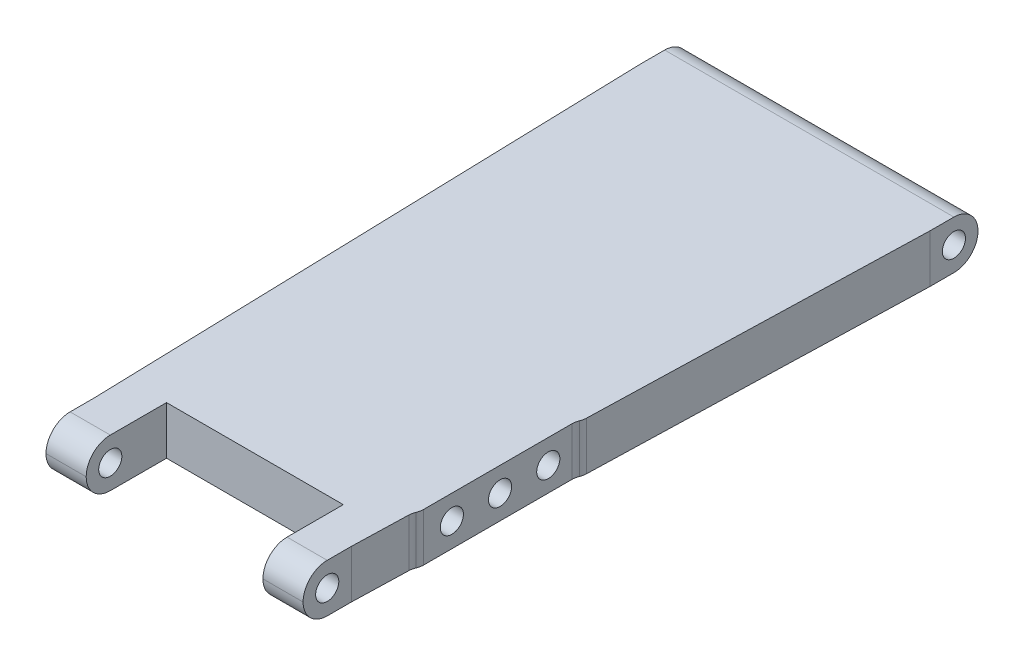
SolidWorks part; units mm, degrees
ref_plane "Front Plane" through (0, 0, 0) normal (0, 0, 1) x (1, 0, 0)
ref_plane "Top Plane" through (0, 0, 0) normal (0, 1, 0) x (1, 0, 0)
ref_plane "Right Plane" through (0, 0, 0) normal (1, 0, 0) x (0, 0, -1)
sketch "Sketch1" plane through (0, 0, 0) normal (0, 1, 0) x (1, 0, 0)
  line L0 (0, 0) -> (0, -120.65) construction
  line L1 (-28.575, 0) -> (28.575, 0) construction
  line L2 (-28.575, 4.7625) -> (-28.575, -4.7625)
  line L3 (28.575, 4.7625) -> (28.575, -4.7625)
  line L4 (-25.4, -120.65) -> (25.4, -120.65) construction
  line L5 (-25.4, -115.8875) -> (-25.4, -125.4125)
  line L6 (25.4, -115.8875) -> (25.4, -125.4125)
  line L7 (-28.575, -4.7625) -> (-25.4, -115.8875)
  line L8 (28.575, -4.7625) -> (25.4, -115.8875)
  line L9 (-25.4, -125.4125) -> (25.4, -125.4125)
  line L11 (-17.4625, -125.4125) -> (-17.4625, -109.5375)
  line L12 (-17.4625, -109.5375) -> (17.4625, -109.5375)
  line L13 (-28.575, 4.7625) -> (28.575, 4.7625)
  line L14 (-28.575, -4.7625) -> (28.575, -4.7625)
  line L15 (-25.4, -115.8875) -> (25.4, -115.8875)
  line L16 (-19.05, 4.7625) -> (-19.05, -4.7625)
  line L17 (-19.05, -4.7625) -> (19.05, -4.7625)
  line L18 (19.05, -4.7625) -> (19.05, 4.7625)
  line L19 (17.4625, -109.5375) -> (17.4625, -125.4125)
  line L20 (26.2164, -71.4375) -> (26.2164, -103.1875)
  line L21 (26.2164, -103.1875) -> (25.7629, -103.1875)
  line L22 (26.2164, -71.4375) -> (26.67, -71.4375)
  point P6 (0, 0)
  point P9 (-28.575, 0)
  point P11 (28.575, 0)
  point P16 (0, -120.65)
  point P18 (-25.4, -120.65)
  point P21 (25.4, -120.65)
  dimension "D1" = 9.525
  dimension "D2" = 57.15
  dimension "D3" = 9.525
  dimension "D4" = 50.8
  dimension "D5" = 120.65
  dimension "D6" = 7.9375
  dimension "D7" = 7.9375
  dimension "D11" = 31.75
  dimension "D12" = 76.2
  dimension "D8" = 9.525
  dimension "D9" = 9.525
  dimension "D10" = 15.875
extrude "Boss-Extrude1" add sketch "Sketch1" along normal blind 9.525 contours L16 L13 L2 L14 | L18 L14 L3 L13 | L7 L15 L8 L14 | L15 L5 L9 | L15 L19 L9 L6 | L14 L18 L13 L16 | L21 L20 L8 region at (-23.8125, 0, 0) region at (-0.0164, 0, 57.1701) region at (0, 0, 0) region at (-21.4312, 0, 120.65) region at (23.8125, 0, 0) region at (21.4312, 0, 120.65) region at (26.0652, 0, 97.8958)
sketch "Sketch6" plane through (-28.575, 0, 0) normal (-1, 0, 0) x (0, 0, 1)
  line L0 (-4.7625, 9.525) -> (-4.7625, 0) construction
  line L1 (115.8875, 9.525) -> (125.4125, 9.525) construction
  circle A0 centre (0, 4.7625) radius 2.286
  circle A1 centre (120.65, 4.7625) radius 2.286
  point P2 (-4.7625, 4.7625)
  point P3 (0, 0)
  point P10 (120.65, 9.525)
  dimension "D1" = 4.572
extrude "Cut-Extrude2" cut sketch "Sketch6" against normal through all both and the other way through all
fillet "Fillet5" radius 4.7625 6 edges at (0, 0, -4.7625) (0, 9.525, -4.7625) (21.4312, 0, 125.4125) (-21.4312, 0, 125.4125) (-21.4312, 9.525, 125.4125) (21.4312, 9.525, 125.4125)
sketch "Sketch7" plane through (26.2164, 0, 0) normal (1, 0, 0) x (0, 0, -1)
  line L0 (-96.8375, 4.7625) -> (-87.3125, 4.7625) construction
  line L1 (-87.3125, 4.7625) -> (-77.7875, 4.7625) construction
  line L4 (-103.1875, 0) -> (-71.4375, 0)
  line L5 (-71.4375, 0) -> (-71.4375, 9.525)
  line L6 (-71.4375, 9.525) -> (-103.1875, 9.525)
  line L7 (-103.1875, 9.525) -> (-103.1875, 0)
  line L8 (-103.1875, 0) -> (-71.4375, 0)
  line L9 (-71.4375, 0) -> (-71.4375, 9.525)
  line L10 (-71.4375, 9.525) -> (-103.1875, 9.525)
  line L11 (-103.1875, 9.525) -> (-103.1875, 0)
  circle A0 centre (-96.8375, 4.7625) radius 2.286
  circle A1 centre (-87.3125, 4.7625) radius 2.286
  circle A2 centre (-77.7875, 4.7625) radius 2.286
  point P11 (-103.1875, 4.7625)
  dimension "D2" = 4.572
  dimension "D3" = 6.35
  dimension "D4" = 6.35
  dimension "D1" = 0
fillet "Fillet6" radius 3.175 2 edges at (25.7629, 4.7625, 103.1875) (26.2164, 4.7625, 71.4375)
fillet "Fillet7" radius 3.175 2 edges at (26.67, 4.7625, 71.4375) (26.2164, 4.7625, 103.1875)
extrude "Cut-Extrude4" cut sketch "Sketch7" against normal blind 4.7625 contours A0 | A1 | A2 region at (26.2164, 4.7625, 96.8375) region at (26.2164, 4.7625, 87.3125) region at (26.2164, 4.7625, 77.7875)
